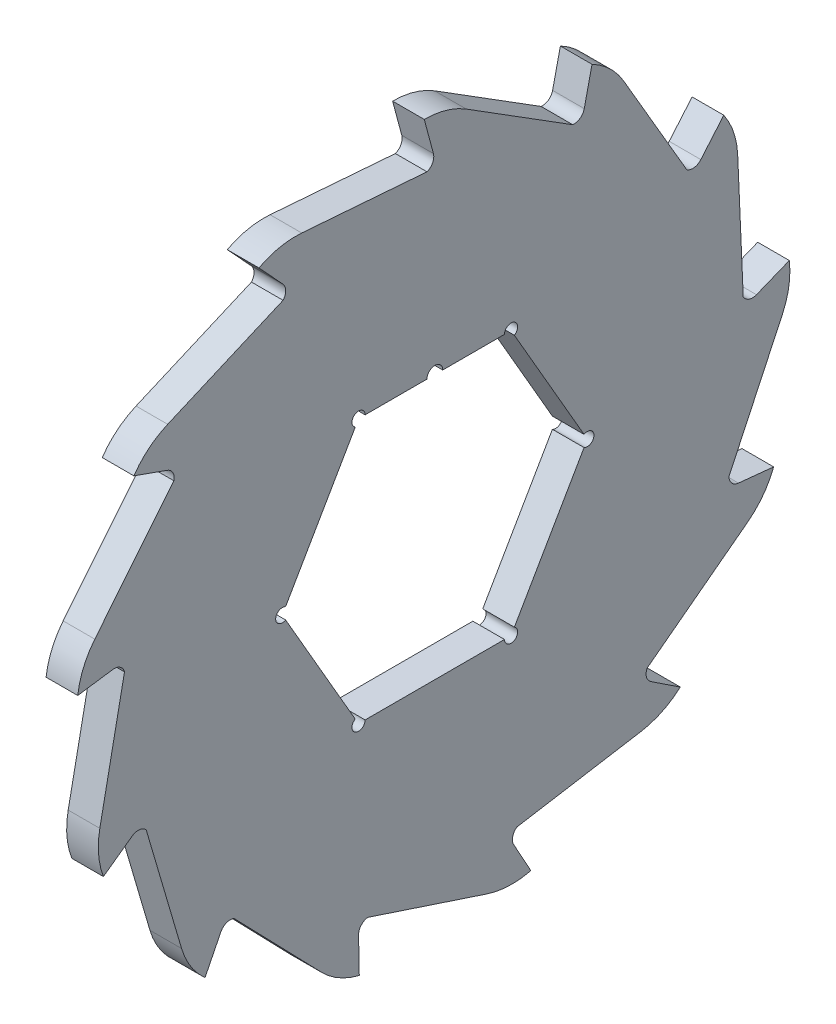
SolidWorks part; units mm, degrees
material "1.0037 (S235JR)"
ref_plane "Alzado" through (0, 0, 0) normal (0, 0, 1) x (1, 0, 0)
ref_plane "Planta" through (0, 0, 0) normal (0, 1, 0) x (1, 0, 0)
ref_plane "Vista lateral" through (0, 0, 0) normal (1, 0, 0) x (0, 0, -1)
sketch "Sketch1" plane through (0, 0, 0) normal (1, 0, 0) x (0, 0, -1)
  line L0 (-56.6126, 0) -> (65.57, 0) construction
  line L1 (14.4626, 25.05) -> (-14.4626, 25.05)
  line L2 (-14.4626, 25.05) -> (-28.9252, 0)
  line L3 (-28.9252, 0) -> (-14.4626, -25.05)
  line L4 (-14.4626, -25.05) -> (14.4626, -25.05)
  line L5 (14.4626, -25.05) -> (28.9252, 0)
  line L6 (28.9252, 0) -> (14.4626, 25.05)
  circle A0 centre (0, 0) radius 25.05 construction
  circle A1 centre (0, 0) radius 59
  dimension "D2" = 118
  dimension "D1" = 50.1
  dimension "D3" = 0
extrude "Extrude1" add sketch "Sketch1" along normal mid plane 6
ref_axis "Axis1" through (-5.5, 0, 0) along (1, 0, 0)
sketch "Sketch2" plane through (0, 0, 0) normal (1, 0, 0) x (0, 0, -1)
  line L0 (-2, 67.9618) -> (-0.2627, 61.4781)
  line L1 (0, 0) -> (0, 77.6328) construction
  line L2 (26.7008, 52.6679) -> (5.9696, 65.6695)
  line L3 (-2.1226, 58.9618) -> (0, 0) construction
  line L4 (0, 0) -> (27.6427, 52.1237) construction
  circle A0 centre (0, 0) radius 59 construction
  arc A1 (-2, 67.9618) -> (5.9696, 65.6695) centre (-2, 52.9618) cw
  arc A3 (27.6427, 52.1237) -> (-2.1226, 58.9618) centre (0, 0) ccw
  arc A4 (-0.2627, 61.4781) -> (-2.1226, 58.9618) centre (-2.1946, 60.9605) cw
  arc A5 (26.7008, 52.6679) -> (27.6427, 52.1237) centre (34.6705, 65.3755) ccw
  point P13 (-2, 67.9618)
  dimension "D2" = 15
  dimension "D4" = 2
  dimension "D3" = 9
  dimension "D7" = 15
  dimension "D1" = 15
  dimension "D5" = 2
  dimension "D6" = 30
extrude "Extrude2" add sketch "Sketch2" against normal mid plane 6
fillet "Fillet1" [suppressed] radius 0.6
pattern_circular "CirPattern1" count 13 over 360 about axis through (-5.5, 0, 0) along (1, 0, 0) of "Extrude2", "Fillet1"
sketch "Sketch3" [suppressed] plane through (3, 0, 0) normal (1, 0, 0) x (0, 0, -1)
  circle A0 centre (0, 0) radius 67.9496 construction
  dimension "D1" = 135.8992
hole_wizard "Ø2.5 (2.5) Diameter Hole1" positions "Sketch4" profile "Sketch5" hole size "Ø2.5" standard "ISO" end condition up to next
sketch "Sketch4" plane through (3, 0, 0) normal (1, 0, 0) x (0, 0, -1)
  point P0 (-14.4626, 25.05)
  point P3 (14.4626, 25.05)
  point P6 (28.9252, 0)
  point P9 (14.4626, -25.05)
  point P12 (-14.4626, -25.05)
  point P15 (-28.9252, 0)
sketch "Sketch5" plane through (3, 25.05, 14.4626) normal (0, 1, 0) x (0, 0, -1)
  line L0 (0, 0) -> (0, 6)
  line L1 (0, 6) -> (1.25, 6)
  line L2 (1.25, 6) -> (1.25, 0)
  line L5 (1.25, 0) -> (0, 0)
  line L11 (0, -6.35) -> (0, 107.95) construction
  dimension "Diámetro de taladro hasta el siguiente" = 2.5
  dimension "Profundidad de taladro hasta el siguiente" = 6
hole_wizard "Ø3.0 (3) Diameter Hole1" positions "Sketch6" profile "Sketch7" hole size "Ø3.0" standard "ISO" end condition up to next
sketch "Sketch6" plane through (3, 0, 0) normal (1, 0, 0) x (0, 0, -1)
  line L0 (13.2126, 25.05) -> (-13.2126, 25.05) construction
  point P19 (0, 25.05)
sketch "Sketch7" plane through (3, 25.05, 0) normal (0, 1, 0) x (0, 0, -1)
  line L0 (0, 0) -> (0, 6)
  line L1 (0, 6) -> (1.5, 6)
  line L2 (1.5, 6) -> (1.5, 0)
  line L5 (1.5, 0) -> (0, 0)
  line L11 (0, -6.35) -> (0, 107.95) construction
  dimension "Diámetro de taladro hasta el siguiente" = 3
  dimension "Profundidad de taladro hasta el siguiente" = 6
equation "\"D1@Extrude2\"=\"D1@Extrude1\""
